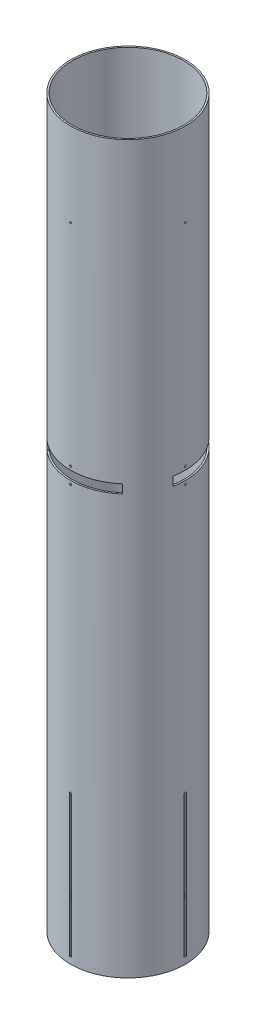
SolidWorks part; units mm, degrees
material "A-Glass Fiber"
ref_plane "Front Plane" through (0, 0, 0) normal (0, 0, 1) x (1, 0, 0)
ref_plane "Top Plane" through (0, 0, 0) normal (0, 1, 0) x (1, 0, 0)
ref_plane "Right Plane" through (0, 0, 0) normal (1, 0, 0) x (0, 0, -1)
sketch "Sketch1" plane through (0, 0, 0) normal (0, 1, 0) x (1, 0, 0)
  circle A0 centre (0, 0) radius 76.2
  circle A1 centre (0, 0) radius 78.359
  dimension "D1" = 152.4
  dimension "D2" = 156.718
extrude "Boss-Extrude1" add sketch "Sketch1" along normal blind 990.6
ref_plane "Plane1" through (0, 0, 0) normal (0.7071, 0, 0.7071) x (0.7071, 0, -0.7071)
ref_axis "Axis1" through (0, 990.6, 0) along (0, -1, 0)
sketch "Sketch2" plane through (0, 0, 0) normal (1, 0, 0) x (0, 0, -1)
  line L0 (0, 0) -> (0, 8.89)
  line L1 (1.5875, 8.89) -> (-1.5875, 8.89)
  line L2 (1.5875, 8.89) -> (1.5875, 203.2)
  line L3 (1.5875, 203.2) -> (-1.5875, 203.2)
  line L4 (-1.5875, 8.89) -> (-1.5875, 203.2)
  line L5 (1.5875, 8.89) -> (-1.5875, 203.2) construction
  line L6 (1.5875, 203.2) -> (-1.5875, 8.89) construction
  line L7 (78.359, 990.6) -> (-78.359, 990.6) construction
  line L8 (78.359, 990.6) -> (-78.359, 990.6)
  line L9 (0, 990.6) -> (0, 588.645)
  line L10 (-78.359, 0) -> (78.359, 0) construction
  circle A0 centre (0, 588.645) radius 1.3525
  circle A1 centre (0, 876.3) radius 1.0922
  point P0 (0, 106.045)
  dimension "D4" = 2.7051
  dimension "D6" = 2.1844
  dimension "D1" = 3.175
  dimension "D2" = 194.31
  dimension "D5" = 588.645
  dimension "D3" = 203.2
  dimension "D7" = 114.3
extrude "Fin Slots" cut sketch "Sketch2" against normal through all contours L4 L1 L2 L3 region at (0, 106.045, 0)
pattern_circular "CirPattern1" count 4 over 360 about axis through (0, 0, 0) along (0, 1, 0) of "Fin Slots" reverse direction yes
extrude "Cut-Extrude2" cut sketch "Sketch2<3>" against normal through all contours A0 region at (0, 589.5743, -0.9293)
sketch "Sketch2<3>" plane through (0, 0, 0) normal (1, 0, 0) x (0, 0, -1) same geometry as "Sketch2"
pattern_circular "CirPattern2" count 4 over 360 about axis through (0, 990.6, 0) along (0, -1, 0) of "Cut-Extrude2"
sketch "Sketch3" plane through (0, 0, 0) normal (0.7071, 0, 0.7071) x (0.7071, 0, -0.7071)
  line L0 (0, 0) -> (0, 127) construction
  circle A0 centre (0, 127) radius 3.175
  dimension "D1" = 6.35
  dimension "D2" = 127
extrude "Cut-Extrude3" cut sketch "Sketch3" against normal through all
ref_plane "Plane3" through (0, 583.8825, 0) normal (0, 1, 0) x (1, 0, 0)
sketch "Sketch7" plane through (0, 583.8825, 0) normal (0, 1, 0) x (1, 0, 0)
  line L0 (0, 0) -> (-76.8534, -15.2871)
  line L1 (0, 0) -> (0, 93.232) construction
  line L2 (0, 0) -> (-25.1877, 74.2005)
  line L3 (-78.359, 0) -> (0, 0) construction
  arc A0 (-78.3473, 1.3526) -> (-78.3473, -1.3525) centre (0, 0) ccw construction
  circle A1 centre (0, 0) radius 76.2 construction
  circle A2 centre (0, 0) radius 78.359
  circle A3 centre (0, 0) radius 78.359
  circle A4 centre (0, 0) radius 76.2
  circle A5 centre (0, 0) radius 78.359 construction
  arc A6 (1.3526, 78.3473) -> (-1.3525, 78.3473) centre (0, 0) ccw construction
  arc A7 (-78.3473, 1.3526) -> (-78.3473, -1.3525) centre (0, 0) ccw
  arc A8 (1.3526, 78.3473) -> (-1.3525, 78.3473) centre (0, 0) ccw
  dimension "D1" = 82.5
  dimension "D3" = 11.25
  dimension "D2" = 0
extrude "Cut-Extrude4" cut sketch "Sketch7" against normal blind 12.065 contours A4 A3 L0 region at (-75.9984, 583.8825, 14.0521)
pattern_circular "CirPattern3" count 3 over 360 about axis through (0, 990.6, 0) along (0, -1, 0) of "Cut-Extrude4"
extrude "Shear Screw Holes" cut sketch "Sketch2<4>" against normal through all contours L9 A1 | L9 A1 region at (0, 876.3, -0.4635) region at (0, 876.3, 0.4635)
sketch "Sketch2<4>" plane through (0, 0, 0) normal (1, 0, 0) x (0, 0, -1) same geometry as "Sketch2"
pattern_circular "Shear Screw Pattern" count 4 over 360 about axis through (0, 990.6, 0) along (0, -1, 0) of "Shear Screw Holes"
pattern_linear "LPattern1" count 2 spacing 21.524 along (0, -1, 0) of "Cut-Extrude2", "CirPattern2"
equation "\"D1@Boss-Extrude1\" = \"Aft_Section_Length\""
equation "\"AB_Coupler_OD_Length\"= 1in"
equation "\"AB_Coupling_Section_Length\"= 0.375in"
equation "\"AB_Coupler_Length\"= \"AB_Coupler_OD_Length\" + \"AB_Coupling_Section_Length\" * 2"
equation "\"AB_Coupler_Num_Screws\"= 4"
equation "\"AB_Coupling_Screw_Diameter\"= 0.1065in"
equation "\"Aft_Section_Length\"= 39in"
equation "\"D4@Sketch2\"=\"AB_Coupling_Screw_Diameter\""
equation "\"D1@CirPattern2\"=\"AB_Coupler_Num_Screws\""
equation "\"Rail_Nut_From_Bottom\"= 5in"
equation "\"Rail_Nut_Diam\"= 0.25in"
equation "\"D1@Sketch3\"=\"Rail_Nut_Diam\""
equation "\"D2@Sketch3\"=\"Rail_Nut_From_Bottom\""
equation "\"AB_BKHD_Thickness\" = 0.375in"
equation "\"AB_Mount_From_Bottom\" = 23.175in"
equation "\"Cutout_Angle\" = 80"
equation "\"Shear_Screw_Diameter\" = 0.086in"
equation "\"D6@Sketch2\"=\"Shear_Screw_Diameter\""
equation "\"Shear_Screw_Coupler_Location\" = 4.5in"
equation "\"D7@Sketch2\"=\"Shear_Screw_Coupler_Location\""
equation "\"Bodytube_OD\" = 6.17in"
equation "\"Bodytube_ID\" = 5.998in"
equation "\"Motor_OD\" = 4in"
equation "\"Fwd_Tube_Length\" = 40in"
equation "\"Mid_Tube_Length\" = 1in"
equation "\"Mid_Coupler_Length\" = 13in"
equation "\"AB_Paddle_Height\" = 0.375in"
equation "\"Num_Cutouts\" = 3"
equation "\"AB_Coupler_OD\"= 6.17in"
equation "\"AB_Coupler_ID\"= 5.75in"
equation "\"AB_Coupler_Surface_Diameter\"= 5.998in"
equation "\"AB_Central_Bushing_Length\" = .4724in"
equation "\"Lead_Screw_Dist\" = 3.4in"
equation "\"Lead_Screw_Diam\" = 0.386in"
equation "\"Lead_Screw_Length\" = (\"Mid_Coupler_Length\" + 2*0.375in + 2*0.5in)"
equation "\"Paddle_Pin_Offset\" = .25in"
equation "\"Paddle_Pin_Radius\" = 2.25in"
equation "\"SS_Paddle_Pin_Radius\" = 2.25*0.66in"
equation "\"Paddle_Gear_OD\" = 3.2in"
equation "\"Drive_Gear_OD\" = 1.7in"
equation "\"Fwd_BKHD_From_Top\" = 18in"
equation "\"Fin_Thickness\"= .118in"
equation "\"Guiderail_Cutout_Diameter\"= 1.5in"
equation "\"DB9_Hole_Dist\" = 25mm"
equation "\"DB9_Relief_Width\" = 0.47in"
equation "\"DB9_Relief_Hole_Offset\" = 0.09in"
equation "\"Airbrakes_Wire_Hole_Dia\" = .25in"
equation "\"Airbrakes_Wire_Hole_Dist\" = 1.1in"
equation "\"Servo_Gear_Offset\" = 0.5in"
equation "\"D3@LPattern1\"=\"AB_Central_Bushing_Length\"+\"AB_Coupling_Section_Length\""
